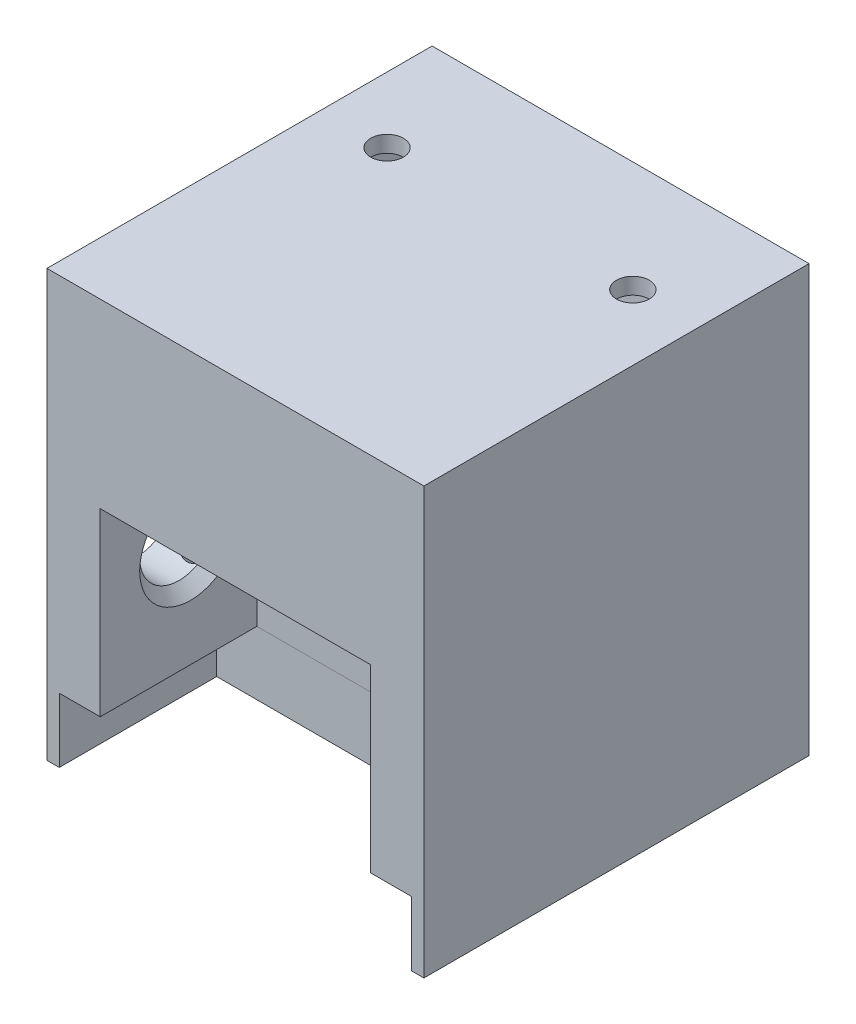
SolidWorks part; units mm, degrees
ref_plane "Front Plane" through (0, 0, 0) normal (0, 0, 1) x (1, 0, 0)
ref_plane "Top Plane" through (0, 0, 0) normal (0, 1, 0) x (1, 0, 0)
ref_plane "Right Plane" through (0, 0, 0) normal (1, 0, 0) x (0, 0, -1)
sketch "Sketch1" plane through (0, 0, 0) normal (0, 1, 0) x (1, 0, 0)
  line L0 (0, 25.4073) -> (0, -25.4073) construction
  line L1 (-29.21, 17.145) -> (29.21, 17.145)
  line L2 (-24.13, -12.065) -> (-1.27, -12.065)
  line L3 (-24.13, -12.065) -> (-24.13, 12.065)
  line L4 (-24.13, 12.065) -> (-1.27, 12.065)
  line L5 (24.13, -12.065) -> (24.13, 12.065)
  line L6 (-24.13, -12.065) -> (24.13, 12.065) construction
  line L7 (-24.13, 12.065) -> (24.13, -12.065) construction
  line L8 (12.065, 9.525) -> (12.065, -9.525) construction
  line L9 (2.54, 0) -> (21.59, 0) construction
  line L10 (29.21, -17.145) -> (29.21, 17.145)
  line L11 (-29.21, -17.145) -> (29.21, -17.145) construction
  line L12 (-29.21, -17.145) -> (-29.21, 17.145)
  line L13 (-1.27, 12.065) -> (-1.27, -12.065)
  line L14 (1.27, 12.065) -> (1.27, -12.065)
  line L15 (-1.27, 25.4073) -> (-1.27, -25.4073) construction
  line L16 (1.27, 25.4073) -> (1.27, -25.4073) construction
  line L17 (1.27, 12.065) -> (24.13, 12.065)
  line L18 (-24.13, 12.065) -> (24.13, 12.065) construction
  line L19 (1.27, -12.065) -> (24.13, -12.065)
  line L20 (-24.13, -12.065) -> (24.13, -12.065) construction
  line L21 (-29.21, -17.145) -> (-29.21, -42.545)
  line L22 (-29.21, -42.545) -> (29.21, -42.545)
  line L23 (29.21, -42.545) -> (29.21, -17.145)
  circle A0 centre (-12.065, 0) radius 9.525 construction
  circle A1 centre (12.065, 0) radius 9.525 construction
  point P7 (0, 0)
  dimension "D1" = 19.05
  dimension "D2" = 2.54
  dimension "D3" = 2.54
  dimension "D4" = 2.54
  dimension "D8" = 25.4
  dimension "D5" = 5.08
  dimension "D6" = 1.27
  dimension "D7" = 1.27
extrude "Boss-Extrude1" add sketch "Sketch1" along normal blind 63.5
sketch "Sketch2" plane through (0, 63.5, 0) normal (0, 1, 0) x (1, 0, 0)
  line L0 (-29.21, 17.145) -> (29.21, 17.145) construction
  line L1 (-29.21, 17.145) -> (29.21, 17.145)
  line L3 (29.21, -42.545) -> (29.21, 17.145) construction
  line L4 (-29.21, -42.545) -> (-29.21, 17.145) construction
  line L6 (29.21, -42.545) -> (29.21, 17.145)
  line L7 (-29.21, -42.545) -> (-29.21, 17.145)
  line L8 (-29.21, -42.545) -> (29.21, -42.545) construction
  line L9 (-29.21, -42.545) -> (29.21, -42.545)
extrude "Boss-Extrude2" add sketch "Sketch2" along normal blind 2.54 contours L6 L1 L7 L9
sketch "Sketch3" plane through (0, 66.04, 0) normal (0, 1, 0) x (1, 0, 0)
  line L0 (0, 10.177) -> (0, -6.9303) construction
  circle A0 centre (-19.05, 0) radius 2.54
  circle A1 centre (19.05, 0) radius 2.54
  dimension "D1" = 5.08
  dimension "D2" = 38.1
extrude "Cut-Extrude1" cut sketch "Sketch3" against normal through all
sketch "Sketch6" plane through (0, 0, 0) normal (0, -1, 0) x (1, 0, 0)
  line L0 (-29.21, 27.9466) -> (29.21, 27.9466) construction
  line L1 (-27.305, 38.9712) -> (27.305, 38.9712)
  line L2 (-27.305, 38.9712) -> (-27.305, 18.1432)
  line L3 (-27.305, 18.1432) -> (27.305, 18.1432)
  line L4 (27.305, 38.9712) -> (27.305, 18.1432)
  line L5 (-29.21, 42.545) -> (-29.21, -17.145) construction
  line L6 (29.21, 42.545) -> (29.21, -17.145) construction
  line L7 (0, 0) -> (0, 27.9466) construction
  point P10 (0, 27.9466)
  point P11 (0, 18.1432)
  dimension "D1" = 54.61
  dimension "D2" = 20.828
  dimension "D3" = 27.9466
extrude "Cut-Extrude3" cut sketch "Sketch6" against normal blind 9.9794
sketch "Sketch7" plane through (0, 9.9794, 0) normal (0, -1, 0) x (1, 0, 0)
  circle A4 centre (24.09, 36.9309) radius 2.2352
  circle A5 centre (24.09, 23.7574) radius 2.2352
  circle A6 centre (-24.09, 23.7574) radius 2.2352
  circle A7 centre (-24.09, 36.9309) radius 2.2352
  dimension "D1" = 4.4704
extrude "Cut-Extrude4" cut sketch "Sketch7" against normal blind 12.7
sketch "Sketch9" plane through (0, 9.9794, 0) normal (0, -1, 0) x (1, 0, 0)
  line L0 (0, 38.9712) -> (0, 18.1432) construction
  line L1 (27.305, 38.9712) -> (-27.305, 38.9712) construction
  line L2 (-27.305, 18.1432) -> (27.305, 18.1432) construction
  line L3 (-27.305, 28.5572) -> (27.305, 28.5572) construction
  line L4 (-27.305, 38.9712) -> (-27.305, 18.1432) construction
  line L5 (27.305, 18.1432) -> (27.305, 38.9712) construction
  line L7 (20.955, 18.2702) -> (-20.955, 18.2702)
  line L8 (20.955, 18.2702) -> (20.955, 38.8442)
  line L9 (20.955, 38.8442) -> (-20.955, 38.8442)
  line L10 (-20.955, 18.2702) -> (-20.955, 38.8442)
  line L11 (20.955, 18.2702) -> (-20.955, 38.8442) construction
  line L12 (20.955, 38.8442) -> (-20.955, 18.2702) construction
  point P12 (0, 28.5572)
  dimension "D1" = 41.91
  dimension "D2" = 20.574
extrude "Cut-Extrude5" cut sketch "Sketch9" against normal blind 27.94
sketch "Sketch10" plane through (-20.955, 0, 0) normal (1, 0, 0) x (0, 0, -1)
  line L8 (-38.8442, 9.9794) -> (-18.2702, 9.9794)
  line L9 (-18.2702, 9.9794) -> (-18.2702, 37.9194)
  line L10 (-18.2702, 37.9194) -> (-38.8442, 37.9194)
  line L11 (-38.8442, 37.9194) -> (-38.8442, 9.9794)
  line L12 (-38.8442, 9.9794) -> (-18.2702, 9.9794) construction
  line L13 (-18.2702, 9.9794) -> (-18.2702, 37.9194) construction
  line L14 (-18.2702, 37.9194) -> (-38.8442, 37.9194) construction
  line L15 (-38.8442, 37.9194) -> (-38.8442, 9.9794) construction
  circle A0 centre (-28.5572, 26.478) radius 6.096
  point P3 (-28.5572, 37.9194)
  dimension "D3" = 12.192
  dimension "D2" = 11.4414
  dimension "D1" = 0
extrude "Cut-Extrude6" cut sketch "Sketch10" against normal through all
sketch "Sketch11" plane through (0, 0, 38.8442) normal (0, 0, -1) x (-1, 0, 0)
  line L18 (-27.305, 0) -> (27.305, 0) construction
  line L19 (27.305, 0) -> (27.305, 9.9794) construction
  line L20 (27.305, 9.9794) -> (25.0027, 9.9794) construction
  line L21 (25.0027, 9.9794) -> (23.1773, 9.9794) construction
  line L22 (23.1773, 9.9794) -> (-23.1773, 9.9794) construction
  line L23 (-23.1773, 9.9794) -> (-25.0027, 9.9794) construction
  line L24 (-25.0027, 9.9794) -> (-27.305, 9.9794) construction
  line L25 (-27.305, 9.9794) -> (-27.305, 0) construction
  line L27 (20.955, 9.9794) -> (20.955, 37.9194) construction
  line L28 (20.955, 37.9194) -> (-20.955, 37.9194) construction
  line L29 (-20.955, 37.9194) -> (-20.955, 9.9794) construction
  line L30 (-27.305, 0) -> (27.305, 0)
  line L31 (27.305, 0) -> (27.305, 9.9794)
  line L32 (27.305, 9.9794) -> (25.0027, 9.9794)
  line L41 (25.0027, 9.9794) -> (23.1773, 9.9794)
  line L42 (23.1773, 9.9794) -> (20.955, 9.9794)
  line L43 (-23.1773, 9.9794) -> (-25.0027, 9.9794)
  line L44 (-25.0027, 9.9794) -> (-27.305, 9.9794)
  line L45 (-27.305, 9.9794) -> (-27.305, 0)
  line L47 (20.955, 9.9794) -> (20.955, 37.9194)
  line L48 (20.955, 37.9194) -> (-20.955, 37.9194)
  line L49 (-20.955, 37.9194) -> (-20.955, 9.9794)
  line L50 (-20.955, 9.9794) -> (-23.1773, 9.9794)
extrude "Cut-Extrude7" cut sketch "Sketch11" against normal through all
chamfer "Chamfer1" distance 1.778 angle 45 1 edges at (-20.955, 26.478, 22.4612)
